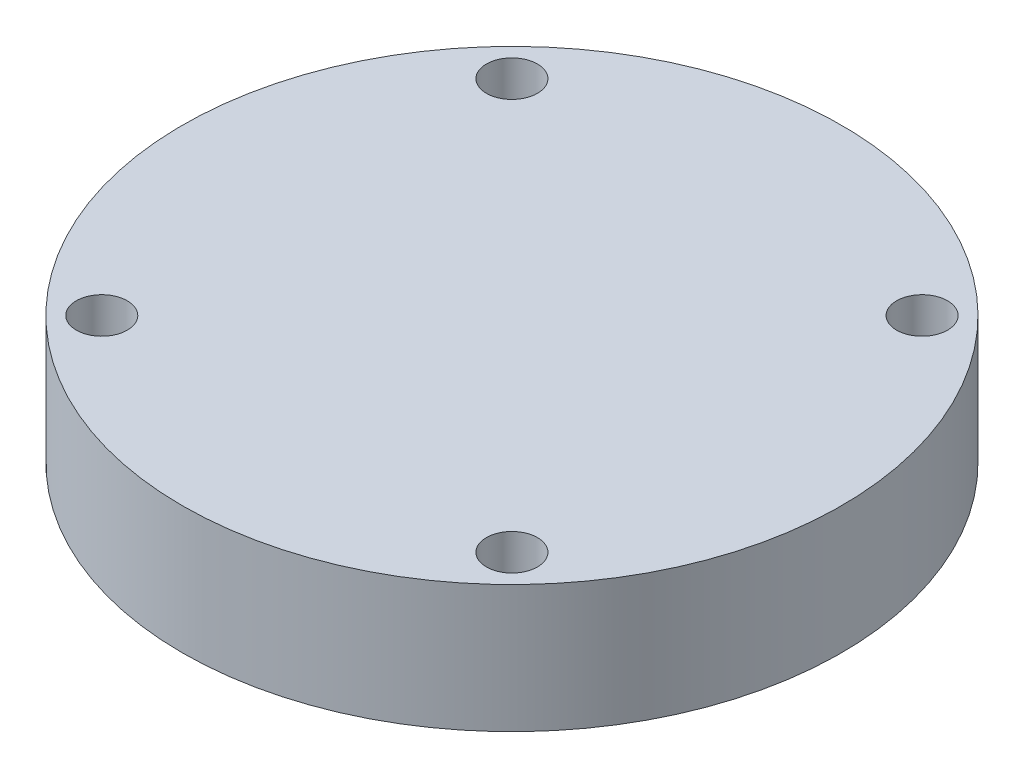
SolidWorks part; units mm, degrees
material "1060 Alloy"
ref_plane "Front Plane" through (0, 0, 0) normal (0, 0, 1) x (1, 0, 0)
ref_plane "Top Plane" through (0, 0, 0) normal (0, 1, 0) x (1, 0, 0)
ref_plane "Right Plane" through (0, 0, 0) normal (1, 0, 0) x (0, 0, -1)
ref_axis "Y Axis" through (0, 7.7343, 0) along (0, -1, 0)
sketch "outer" plane through (0, 0, 0) normal (0, 1, 0) x (1, 0, 0)
  circle A0 centre (0, 0) radius 19.05
  dimension "D1" = 38.1
extrude "Body" add sketch "outer" along normal blind 7.366
sketch "inner" plane through (0, 0, 0) normal (0, 1, 0) x (1, 0, 0)
  circle A0 centre (0, 0) radius 11.811
  dimension "D1" = 23.622
extrude "Pocket" cut sketch "inner" along normal blind 4.826
sketch "Screw Position" plane through (0, 0, 0) normal (0, 1, 0) x (1, 0, 0)
  point P0 (-11.8539, 11.8539)
  dimension "D1" = 16.764
hole_wizard "#4 Clearance Hole1" positions "Sketch7" profile "Sketch8" hole size "#4" standard "ANSI Inch" end condition through all
sketch "Sketch7" plane through (0, 7.366, 0) normal (0, 1, 0) x (1, 0, 0)
  point P0 (-11.8539, 11.8539)
sketch "Sketch8" plane through (-11.8539, 7.366, -11.8539) normal (1, 0, 0) x (0, 0, 1)
  line L0 (0, 0) -> (0, 7.366)
  line L1 (0, 7.366) -> (1.4732, 7.366)
  line L2 (1.4732, 7.366) -> (1.4732, 0)
  line L5 (1.4732, 0) -> (0, 0)
  line L11 (0, -6.35) -> (0, 107.95) construction
  dimension "Thru Hole Dia." = 2.9464
  dimension "Thru Hole Depth" = 7.366
pattern_circular "Screw Holes" count 4 over 360 about axis through (0, 7.7343, 0) along (0, -1, 0) of "#4 Clearance Hole1"
sketch "Post Sketch" plane through (0, 0, 0) normal (0, 1, 0) x (1, 0, 0)
  circle A0 centre (0, -5.715) radius 1.0033
  circle A1 centre (5.2984, -5.2984) radius 1.0033
  point P0 (0, -5.715)
  point P1 (5.2984, -5.2984)
  dimension "D3" = 2.0066
  dimension "D4" = 2.0066
  dimension "D1" = 5.715
extrude "Post" add sketch "Post Sketch" against normal blind 4.826 from surface starting at face at (0, 4.826, 11.811)
pattern_circular "Posts" count 4 over 360 about axis through (0, 7.7343, 0) along (0, -1, 0) of "Post"
sketch "Flat Cut Sketch" plane through (0, 0, 0) normal (0, 1, 0) x (1, 0, 0)
  line L0 (0, 19.05) -> (0, -19.05) construction
  line L1 (-17.78, 19.05) -> (-20.32, -19.05) construction
  line L2 (17.78, -19.05) -> (20.32, -19.05)
  line L3 (17.78, -19.05) -> (17.78, 19.05)
  line L4 (17.78, 19.05) -> (20.32, 19.05)
  line L5 (20.32, -19.05) -> (20.32, 19.05)
  line L6 (17.78, -19.05) -> (20.32, 19.05) construction
  line L7 (17.78, 19.05) -> (20.32, -19.05) construction
  line L8 (-17.78, -19.05) -> (-20.32, 19.05) construction
  line L9 (-20.32, -19.05) -> (-20.32, 19.05)
  line L10 (-17.78, 19.05) -> (-20.32, 19.05)
  line L11 (-17.78, -19.05) -> (-17.78, 19.05)
  line L12 (-17.78, -19.05) -> (-20.32, -19.05)
  circle A0 centre (0, 0) radius 19.05 construction
  point P5 (19.05, 0)
  point P14 (-19.05, 0)
  dimension "D1" = 38.1
  dimension "D2" = 2.54
extrude "Flat Cut" [suppressed] cut sketch "Flat Cut Sketch" along normal through all
equation "\"outer_d\"= 3 / 2in"
equation "\"top_h\"= 1 / 4in"
equation "\"screw_r\"= 0.66in"
equation "\"inner_d\" = 0.93in"
equation "\"inner_h\"= 150mil"
equation "\"D1@outer\" = \"outer_d\""
equation "\"D1@Body\"=\"top_h\" + \"inset_h\""
equation "\"D1@inner\"=\"inner_d\""
equation "\"D1@Pocket\"=\"inner_h\" + \"inset_h\""
equation "\"D1@Screw Position\"=\"screw_r\""
equation "\"post_r1\"= 0.225in"
equation "\"post_r2\" = 0.295in"
equation "\"post_bottom_h\"= 0.04in"
equation "\"D1@Post Sketch\" = \"post_r1\""
equation "\"D2@Post Sketch\" = \"post_r2\""
equation "\"post_d\"= 0.079in"
equation "\"D3@Post Sketch\"=\"post_d\""
equation "\"D4@Post Sketch\"=\"post_d\""
equation "\"D1@Post\" = \"inner_h\" + \"post_bottom_h\""
equation "\"inset_h\"= 0.04in"
equation "\"D1@Flat Cut Sketch\" = \"outer_d\""
equation "\"flat_cut\"= 0.05in"
equation "\"D2@Flat Cut Sketch\" = \"flat_cut\" * 2"
